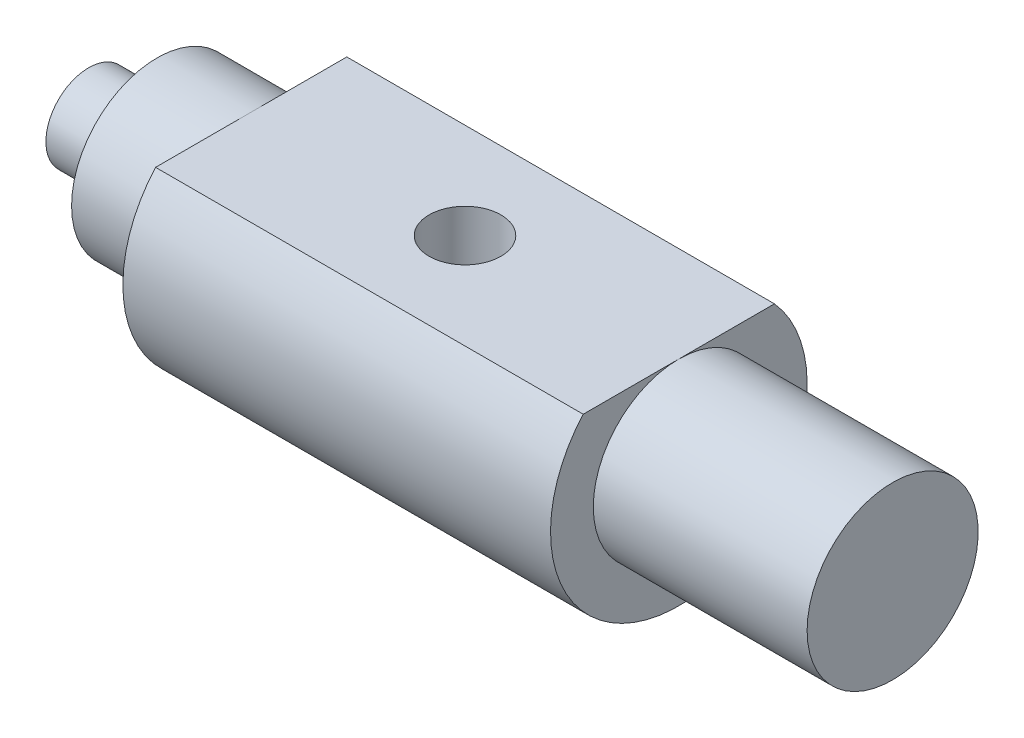
SolidWorks part; units mm, degrees
ref_plane "前视基准面" through (0, 0, 0) normal (0, 0, 1) x (1, 0, 0)
ref_plane "上视基准面" through (0, 0, 0) normal (0, 1, 0) x (1, 0, 0)
ref_plane "右视基准面" through (0, 0, 0) normal (1, 0, 0) x (0, 0, -1)
sketch "草图1" plane through (0, 0, 0) normal (0, 0, 1) x (1, 0, 0)
  line L0 (0, 0) -> (0, 73.8056) construction
  line L1 (0, -6.875) -> (0, 6.875) construction
  line L2 (0, 7.5) -> (12.5, 7.5)
  line L3 (12.5, 7.5) -> (12.5, 5)
  line L4 (12.5, 5) -> (25, 5)
  line L5 (25, 5) -> (25, 0)
  line L6 (12.7722, 0) -> (-12.7722, 0) construction
  line L7 (25, 0) -> (0, 0) construction
  line L8 (0, 7.5) -> (0, 0)
  line L9 (0, 0) -> (25, 0)
  dimension "D1" = 10
  dimension "D2" = 15
  dimension "D3" = 25
  dimension "D4" = 50
revolve "旋转1" add sketch "草图1" angle 360 about L9
mirror "镜向1" about plane through (0, 0, 0) normal (1, 0, 0) of "旋转1"
ref_axis "基准轴1" through (25, 0, 0) along (-1, 0, 0)
sketch "草图2" plane through (0, 0, 0) normal (0, 1, 0) x (1, 0, 0)
  line L1 (-12.5, -11.6111) -> (12.5, -11.6111)
  line L2 (-12.5, -11.6111) -> (-12.5, 11.6111)
  line L3 (-12.5, 11.6111) -> (12.5, 11.6111)
  line L4 (12.5, -11.6111) -> (12.5, 11.6111)
  line L5 (-12.5, -11.6111) -> (12.5, 11.6111) construction
  line L6 (-12.5, 11.6111) -> (12.5, -11.6111) construction
  point P0 (0, 0)
  dimension "D1" = 25
extrude "切除-拉伸1" cut sketch "草图2" along normal through all from offset 5
hole_wizard "M5 螺纹孔的螺纹孔钻头1" positions "草图4" profile "草图5" hole size "M5" standard "GB" end condition up to next
sketch "草图4" plane through (0, 5, 0) normal (0, 1, 0) x (1, 0, 0)
  point P0 (0, 0)
sketch "草图5" plane through (0, 5, 0) normal (1, 0, 0) x (0, 0, 1)
  line L0 (0, 0) -> (0, 12.5)
  line L1 (0, 12.5) -> (2.1, 12.5)
  line L2 (2.1, 12.5) -> (2.1, 0)
  line L5 (2.1, 0) -> (0, 0)
  line L11 (0, -6.35) -> (0, 107.95) construction
  dimension "通孔孔直径" = 4.2
  dimension "通孔孔深度" = 12.5
sketch "草图6" plane through (-25, 0, 0) normal (-1, 0, 0) x (0, 0, 1)
  circle A0 centre (0, 0) radius 2.5
  dimension "D1" = 5
extrude "切除-拉伸2" cut sketch "草图6" against normal blind 7 and the other way through all flip side to cut
sketch "草图7" plane through (-25, 0, 0) normal (-1, 0, 0) x (0, 0, 1)
  circle A1 centre (0, 0) radius 2.5
  circle A2 centre (0, 0) radius 2.5
  dimension "D1" = 0
extrude "切除-拉伸3" cut sketch "草图7" against normal blind 3
hole_wizard "M4 螺纹孔的螺纹孔钻头1" positions "草图8" profile "草图10" hole size "M4" standard "GB"
sketch "草图8" plane through (-22, 0, 0) normal (-1, 0, 0) x (0, 0, 1)
  point P0 (0, 0)
sketch "草图10" plane through (-22, 0, 0) normal (0, 1, 0) x (0, 0, 1)
  line L0 (0, 0) -> (0, 8.9914)
  line L1 (0, 8.9914) -> (1.65, 8)
  line L2 (1.65, 8) -> (1.65, 0)
  line L5 (1.65, 0) -> (0, 0)
  line L10 (0, 8.9914) -> (-1.65, 8) construction
  line L11 (0, -6.35) -> (0, 107.95) construction
  dimension "孔直径" = 3.3
  dimension "孔深度" = 8
  dimension "导头角度" = 118
